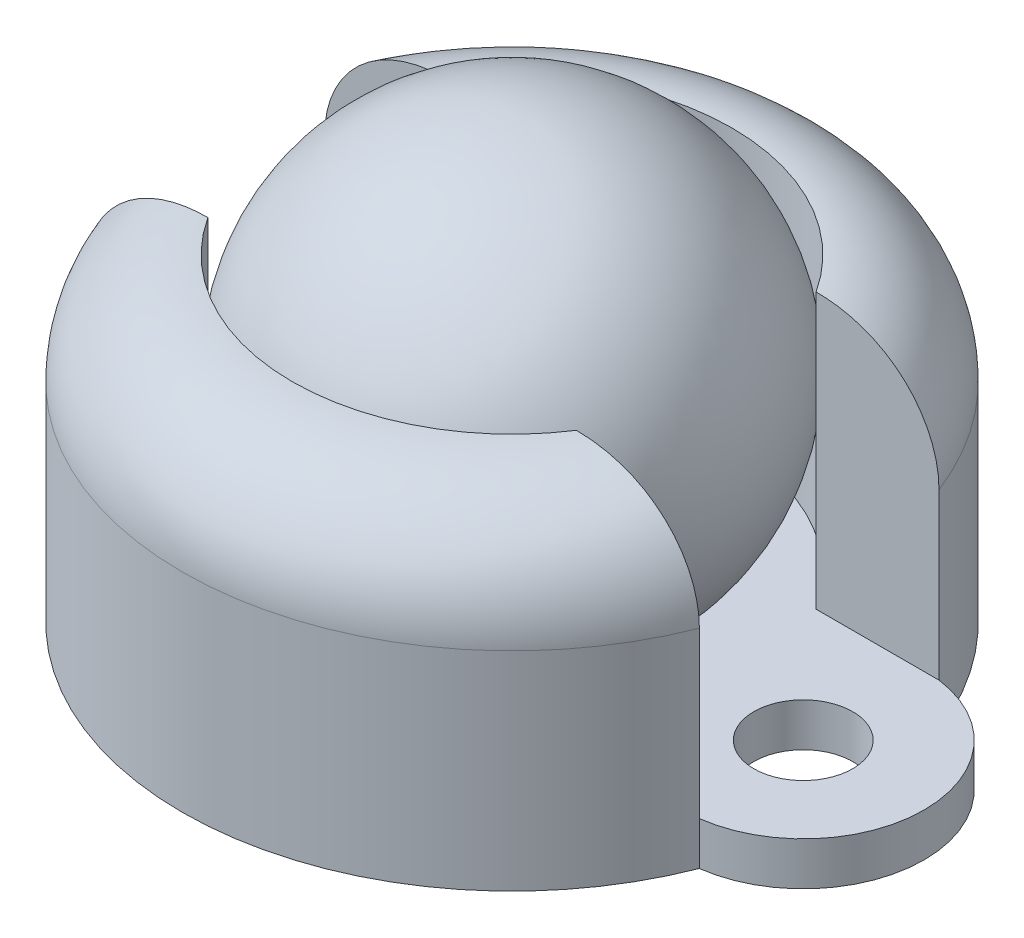
SolidWorks part; units mm, degrees
ref_plane "Front Plane" through (0, 0, 0) normal (0, 0, 1) x (1, 0, 0)
ref_plane "Top Plane" through (0, 0, 0) normal (0, 1, 0) x (1, 0, 0)
ref_plane "Right Plane" through (0, 0, 0) normal (1, 0, 0) x (0, 0, -1)
sketch "Sketch1" plane through (0, 0, 0) normal (0, 1, 0) x (1, 0, 0)
  line L0 (0, 7.62) -> (19.05, 7.62) construction
  line L1 (0, 0) -> (19.05, 0) construction
  line L2 (0, 0) -> (0, 15.24) construction
  line L3 (0, 15.24) -> (19.05, 15.24) construction
  line L4 (19.05, 0) -> (19.05, 15.24) construction
  line L5 (9.525, 15.24) -> (9.525, 0) construction
  arc A0 (2.4262, 10.3897) -> (2.4262, 4.8503) centre (2.794, 7.62) ccw
  arc A1 (16.6238, 4.8503) -> (16.6238, 10.3897) centre (16.256, 7.62) ccw
  arc A2 (16.6238, 10.3897) -> (2.4262, 10.3897) centre (9.525, 7.62) ccw
  circle A3 centre (16.256, 7.62) radius 1.143
  circle A4 centre (2.794, 7.62) radius 1.143
  arc A5 (2.4262, 4.8503) -> (16.6238, 4.8503) centre (9.525, 7.62) ccw
  dimension "D4" = 2.286
  dimension "D1" = 19.05
  dimension "D2" = 15.24
  dimension "D3" = 13.462
extrude "Boss-Extrude1" add sketch "Sketch1" along normal blind 1
sketch "Sketch2" plane through (0, 1, 0) normal (0, 1, 0) x (1, 0, 0)
  line L0 (2.4262, 4.8503) -> (5.2664, 4.8503)
  line L1 (16.6238, 10.3897) -> (13.7836, 10.3897)
  line L2 (5.2664, 10.3897) -> (2.4262, 10.3897)
  line L3 (13.7836, 4.8503) -> (16.6238, 4.8503)
  line L4 (5.2664, 4.8503) -> (13.7836, 4.8503) construction
  line L5 (13.7836, 10.3897) -> (5.2664, 10.3897) construction
  line L6 (19.05, 7.62) -> (0, 7.62) construction
  arc A0 (16.6238, 10.3897) -> (2.4262, 10.3897) centre (9.525, 7.62) ccw construction
  arc A1 (2.4262, 4.8503) -> (16.6238, 4.8503) centre (9.525, 7.62) ccw construction
  arc A2 (16.6238, 10.3897) -> (2.4262, 10.3897) centre (9.525, 7.62) ccw
  arc A3 (2.4262, 4.8503) -> (16.6238, 4.8503) centre (9.525, 7.62) ccw
  arc A4 (5.2664, 4.8503) -> (13.7836, 4.8503) centre (9.525, 7.62) ccw
  arc A5 (13.7836, 10.3897) -> (5.2664, 10.3897) centre (9.525, 7.62) ccw
  arc A6 (14.2575, 9.4665) -> (4.7925, 9.4665) centre (9.525, 7.62) ccw construction
  arc A7 (4.7925, 5.7735) -> (14.2575, 5.7735) centre (9.525, 7.62) ccw construction
  arc A8 (16.6238, 4.8503) -> (16.6238, 10.3897) centre (16.256, 7.62) ccw construction
  arc A9 (2.4262, 10.3897) -> (2.4262, 4.8503) centre (2.794, 7.62) ccw construction
  dimension "D1" = 5.08
extrude "Boss-Extrude2" add sketch "Sketch2" along normal blind 6.35
ref_plane "Plane1" through (0, 0, -7.62) normal (0, 0, -1) x (-1, 0, 0)
sketch "Sketch4" plane through (0, 0, 0) normal (0, -1, 0) x (1, 0, 0)
  circle A0 centre (9.525, -7.62) radius 3.1107
extrude "Cut-Extrude3" cut sketch "Sketch4" against normal up to surface (1 mm away) up to face at (2.794, 1, -6.477)
sketch "Sketch3" plane through (0, 0, -7.62) normal (0, 0, -1) x (-1, 0, 0)
  line L0 (-9.525, 10.16) -> (-9.525, 0) construction
  line L2 (-9.525, 0) -> (-9.525, 10.16)
  arc A0 (-9.525, 0) -> (-9.525, 10.16) centre (-9.525, 5.08) ccw
  dimension "D1" = 10.16
revolve "Revolve3" add sketch "Sketch3" angle 360 about L0
fillet "Fillet1" radius 2.54 2 edges at (9.525, 7.35, 0) (9.525, 7.35, -15.24)
